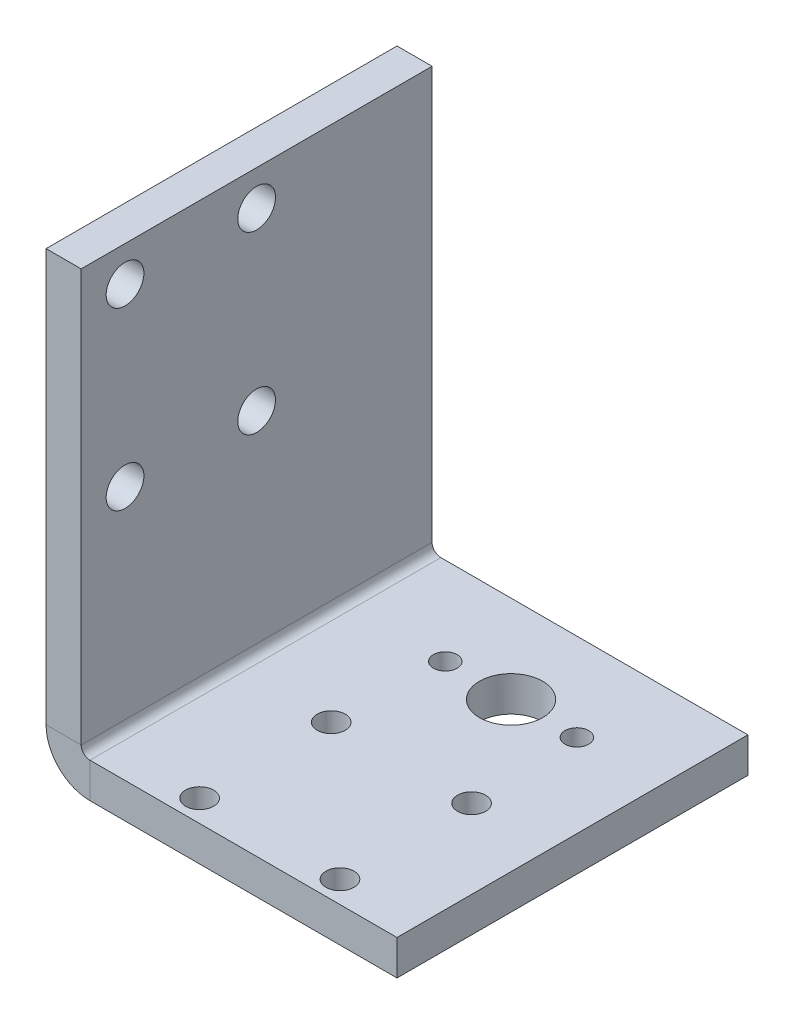
SolidWorks part; units mm, degrees
note: The reader was unsure of these and kept them because the rebuilt part matched: thickness of "基材-凸緣2", "鈑金4", "鈑金5", "鈑金6", "鈑金7", "鈑金8", "鈑金9"; bend radius of "基材彎折1".
material "AISI 304"
ref_plane "前基準面" through (0, 0, 0) normal (0, 0, 1) x (1, 0, 0)
ref_plane "上基準面" through (0, 0, 0) normal (0, 1, 0) x (1, 0, 0)
ref_plane "右基準面" through (0, 0, 0) normal (1, 0, 0) x (0, 0, -1)
sketch "草圖16" plane through (0, 0, 0) normal (0, 0, 1) x (1, 0, 0)
  line L0 (0, 0) -> (0, 48)
  line L1 (0, 0) -> (36, 0)
  dimension "D1" = 36
  dimension "D2" = 48
base flange "基材-凸緣2" sketch "草圖16" end condition mid plane depth 40 reverse direction no thickness 4 reverse thickness direction no bend radius 1
bend "基材彎折1" bend radius 1 bend angle 90 parameters "D5"=1
sketch "草圖21" plane through (-4, 0, 0) normal (-1, 0, 0) x (0, 0, 1)
  line L0 (20, 0) -> (-20, 0) construction
  line L1 (2, 1) -> (15.5, 1)
  line L2 (2, 1) -> (2, 22)
  line L3 (2, 22) -> (15.5, 22)
  line L4 (15.5, 1) -> (15.5, 22)
  line L5 (2, 1) -> (15.5, 22) construction
  line L6 (2, 22) -> (15.5, 1) construction
  line L7 (-20, 48) -> (-20, 1) construction
  line L9 (20, 1) -> (-20, 1) construction
  point P4 (8.75, 11.5)
  dimension "D1" = 22
  dimension "D2" = 13.5
  dimension "D3" = 22
extrude "除料-伸長1" [suppressed] cut sketch "草圖21" against normal blind 20
hole_wizard "M3 餘隙孔1" positions "草圖22" profile "草圖23" hole size "M3" standard "Ansi Metric" end condition through all
sketch "草圖22" plane through (0, 0, 0) normal (0, -1, 0) x (-1, 0, 0)
  line L1 (-11, -2.5) -> (-27, -2.5) construction
  line L2 (-11, -2.5) -> (-11, -17.5) construction
  line L3 (-11, -17.5) -> (-27, -17.5) construction
  line L4 (-27, -2.5) -> (-27, -17.5) construction
  line L5 (-11, -2.5) -> (-27, -17.5) construction
  line L6 (-11, -17.5) -> (-27, -2.5) construction
  line L11 (4, -20) -> (4, 20) construction
  line L13 (-1, -20) -> (-36, -20) construction
  point P2 (-27, -17.5)
  point P57 (-11, -2.5)
  point P58 (-11, -17.5)
  point P59 (-27, -2.5)
  point P95 (-19, -10)
  dimension "D1" = 16
  dimension "D2" = 15
  dimension "D3" = 10
  dimension "D4" = 15
sketch "草圖23" plane through (27, 0, 17.5) normal (1, 0, 0) x (0, 0, 1)
  line L0 (0, 0) -> (0, 4)
  line L1 (0, 4) -> (1.6, 4)
  line L2 (1.6, 4) -> (1.6, 0)
  line L5 (1.6, 0) -> (0, 0)
  line L11 (0, -6.35) -> (0, 107.95) construction
  dimension "砮 ふ 畖" = 3.2
  dimension "砮 ふ瞏 " = 4
sketch "草圖24" plane through (0, -4, 0) normal (0, -1, 0) x (1, 0, 0)
  line L0 (19, 10) -> (19, -10) construction
  line L1 (11, 17.5) -> (27, 17.5) construction
  line L2 (11, 17.5) -> (11, 2.5) construction
  line L3 (11, 2.5) -> (27, 2.5) construction
  line L4 (27, 17.5) -> (27, 2.5) construction
  line L5 (11, 17.5) -> (27, 2.5) construction
  line L6 (11, 2.5) -> (27, 17.5) construction
  circle A0 centre (19, -10) radius 3.6
  point P4 (19, 10)
  point P13 (19, -10)
  dimension "D1" = 7.2
  dimension "D2" = 20
extrude "除料-伸長2" cut sketch "草圖24" against normal through all normal cut yes
hole_wizard "M4 餘隙孔1" positions "草圖27" profile "草圖28" hole size "M4" standard "Ansi Metric" end condition through all
sketch "草圖27" plane through (0, 0, 0) normal (-1, 0, 0) x (0, 0, 1)
  line L1 (15, 44) -> (-15, 44) construction
  line L2 (15, 44) -> (15, 24) construction
  line L3 (15, 24) -> (-15, 24) construction
  line L4 (-15, 44) -> (-15, 24) construction
  line L5 (15, 44) -> (-15, 24) construction
  line L6 (15, 24) -> (-15, 44) construction
  line L7 (0, 0) -> (0, 34) construction
  line L10 (20, 48) -> (-20, 48) construction
  point P104 (15, 44)
  point P105 (15, 24)
  point P133 (0, 24)
  point P135 (0, 44)
  dimension "D1" = 30
  dimension "D2" = 20
  dimension "D3" = 14
sketch "草圖28" plane through (0, 44, 0) normal (0, 1, 0) x (0, 0, -1)
  line L0 (0, 0) -> (0, 4)
  line L1 (0, 4) -> (2.15, 4)
  line L2 (2.15, 4) -> (2.15, 0)
  line L5 (2.15, 0) -> (0, 0)
  line L11 (0, -6.35) -> (0, 107.95) construction
  dimension "砮 ふ 畖" = 4.3
  dimension "砮 ふ瞏 " = 4
hole_wizard "M2.5 餘隙孔1" positions "草圖25" profile "草圖26" hole size "M2.5" standard "Ansi Metric" end condition through all
sketch "草圖25" plane through (0, -4, 0) normal (0, -1, 0) x (-1, 0, 0)
  line L0 (-11.5, 10) -> (-26.5, 10) construction
  circle A0 centre (-19, 10) radius 3.6 construction
  point P0 (-11.5, 10)
  point P1 (-26.5, 10)
  point P4 (-19, 10)
  dimension "D1" = 15
sketch "草圖26" plane through (11.5, -4, -10) normal (1, 0, 0) x (0, 0, -1)
  line L0 (0, 0) -> (0, 52)
  line L1 (0, 52) -> (1.35, 52)
  line L2 (1.35, 52) -> (1.35, 0)
  line L5 (1.35, 0) -> (0, 0)
  line L11 (0, -6.35) -> (0, 107.95) construction
  dimension "砮 ふ 畖" = 2.7
  dimension "砮 ふ瞏 " = 52
sketch "彎折-線3" [suppressed] plane through (0, 0, 0) normal (0, 1, 0) x (1, 0, 0)
sketch "邊界方塊3" [suppressed] plane through (0, 0, 0) normal (0, 1, 0) x (1, 0, 0)
sheet metal parameters "鈑金4" thickness 4 parameters "D1"=1
flat pattern "平板-型式4" [suppressed]
sketch "彎折-線4" plane through (0, 0, 0) normal (0, 1, 0) x (1, 0, 0)
  line L0 (-1.4127, -20) -> (-1.4127, 20) construction
  line L1 (-1.4127, -20) -> (-1.4127, 20) construction
sketch3d "邊界方塊4" [suppressed]
  line L0 (60, 0, 0) -> (-32.8254, 0, 0) construction
  line L1 (60, 40, 0) -> (-32.8254, 40, 0) construction
  line L2 (60, 0, 0) -> (60, 40, 0) construction
  line L3 (-32.8254, 0, 0) -> (-32.8254, 40, 0) construction
bend of the flat pattern "平板-<基材彎折1>1"
sheet metal parameters "鈑金5" thickness 4 parameters "D1"=1
flat pattern "平板-型式4"
sketch "彎折-線4" plane through (0, 0, 0) normal (0, 1, 0) x (1, 0, 0)
  line L0 (-1.4127, -20) -> (-1.4127, -14) construction
  line L1 (-1.4127, -20) -> (-1.4127, -14) construction
  line L2 (-1.4127, 1) -> (-1.4127, 20) construction
sketch3d "邊界方塊4" [suppressed]
  line L0 (60, 0, 0) -> (-42.8254, 0, 0) construction
  line L1 (60, 40, 0) -> (-42.8254, 40, 0) construction
  line L2 (60, 0, 0) -> (60, 40, 0) construction
  line L3 (-42.8254, 0, 0) -> (-42.8254, 40, 0) construction
bend of the flat pattern "平板-<基材彎折1>1"
sheet metal parameters "鈑金6" thickness 4 parameters "D1"=1
flat pattern "平板-型式4"
sketch "彎折-線4" plane through (0, 0, 0) normal (0, 1, 0) x (1, 0, 0)
  line L0 (-1.4127, -20) -> (-1.4127, 20) construction
  line L1 (-1.4127, -20) -> (-1.4127, 20) construction
sketch3d "邊界方塊4" [suppressed]
  line L0 (40, 0, 0) -> (-42.8254, 0, 0) construction
  line L1 (40, 40, 0) -> (-42.8254, 40, 0) construction
  line L2 (40, 0, 0) -> (40, 40, 0) construction
  line L3 (-42.8254, 0, 0) -> (-42.8254, 40, 0) construction
bend of the flat pattern "平板-<基材彎折1>1"
sheet metal parameters "鈑金7" thickness 4 parameters "D1"=1
flat pattern "平板-型式4"
sketch "彎折-線4" plane through (0, 0, 0) normal (0, 1, 0) x (1, 0, 0)
  line L0 (-1.4127, -20) -> (-1.4127, 20) construction
  line L1 (-1.4127, -20) -> (-1.4127, 20) construction
sketch3d "邊界方塊4" [suppressed]
  line L0 (40, 0, 0) -> (-42.8254, 0, 0) construction
  line L1 (40, 40, 0) -> (-42.8254, 40, 0) construction
  line L2 (40, 0, 0) -> (40, 40, 0) construction
  line L3 (-42.8254, 0, 0) -> (-42.8254, 40, 0) construction
bend of the flat pattern "平板-<基材彎折1>1"
sheet metal parameters "鈑金8" thickness 4 parameters "D1"=1
flat pattern "平板-型式4"
sketch "彎折-線4" plane through (0, 0, 0) normal (0, 1, 0) x (1, 0, 0)
  line L0 (-1.3562, -20) -> (-1.3562, 20) construction
  line L1 (-1.3562, -20) -> (-1.3562, 20) construction
sketch3d "邊界方塊4" [suppressed]
  line L0 (36, 0, 0) -> (-50.7124, 0, 0) construction
  line L1 (36, 40, 0) -> (-50.7124, 40, 0) construction
  line L2 (36, 0, 0) -> (36, 40, 0) construction
  line L3 (-50.7124, 0, 0) -> (-50.7124, 40, 0) construction
bend of the flat pattern "平板-<基材彎折1>1"
sheet metal parameters "鈑金9" thickness 4 parameters "D1"=1
flat pattern "平板-型式4"
sketch "彎折-線4" plane through (0, 0, 0) normal (0, 1, 0) x (1, 0, 0)
  line L0 (-1.02, -30) -> (-1.02, 30) construction
  line L1 (-1.02, -30) -> (-1.02, 30) construction
sketch3d "邊界方塊4" [suppressed]
  line L0 (40, 0, 0) -> (-52.04, 0, 0) construction
  line L1 (40, 60, 0) -> (-52.04, 60, 0) construction
  line L2 (40, 0, 0) -> (40, 60, 0) construction
  line L3 (-52.04, 0, 0) -> (-52.04, 60, 0) construction
bend of the flat pattern "平板-<基材彎折1>1"
